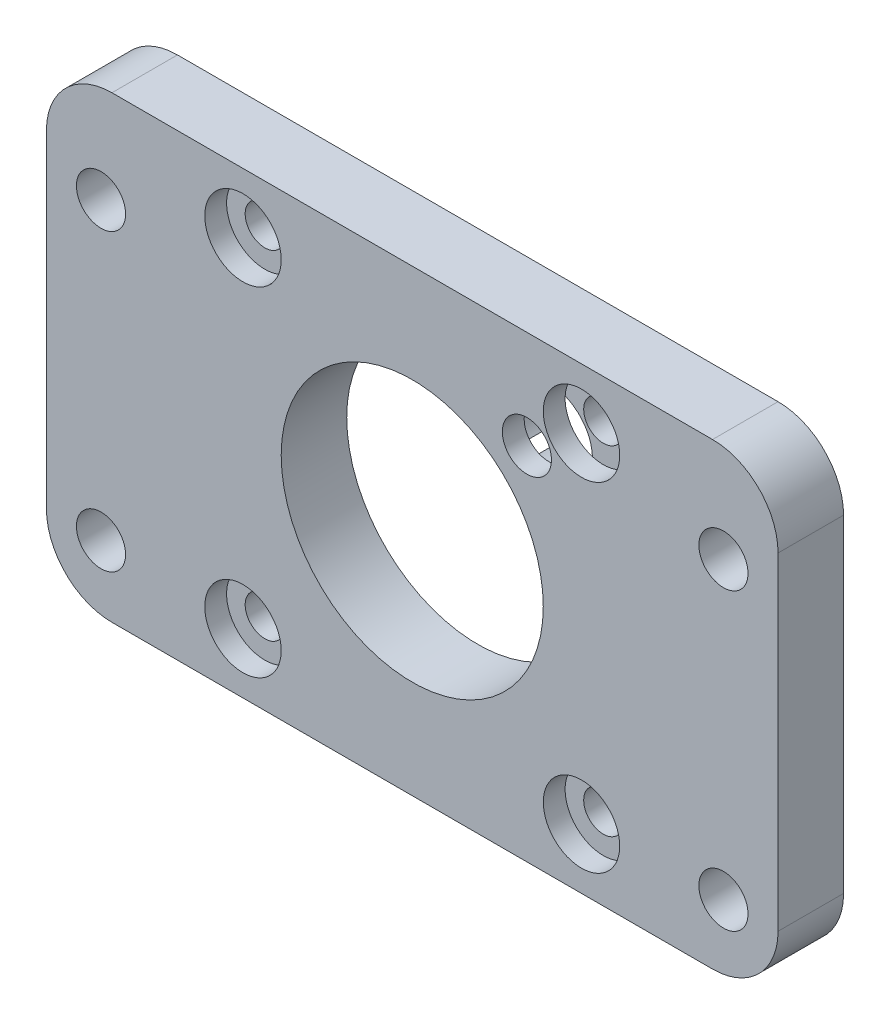
SolidWorks part; units mm, degrees
ref_plane "Спереди" through (0, 0, 0) normal (0, 0, 1) x (1, 0, 0)
ref_plane "Сверху" through (0, 0, 0) normal (0, 1, 0) x (1, 0, 0)
ref_plane "Справа" through (0, 0, 0) normal (1, 0, 0) x (0, 0, -1)
sketch "Эскиз1" plane through (0, 0, 0) normal (0, 0, 1) x (1, 0, 0)
  line L1 (0, 0) -> (67, 0)
  line L2 (0, 0) -> (0, 42)
  line L3 (0, 42) -> (67, 42)
  line L4 (67, 0) -> (67, 42)
  dimension "D1" = 42
  dimension "D2" = 67
extrude "Бобышка-Вытянуть1" add sketch "Эскиз1" along normal blind 6
sketch "Эскиз2" plane through (0, 0, 0) normal (0, 0, -1) x (-1, 0, 0)
  line L0 (-67, 42) -> (0, 42) construction
  line L1 (0, 0) -> (-67, 0) construction
  line L2 (0, 42) -> (0, 0) construction
  line L3 (-67, 0) -> (-67, 42) construction
  circle A0 centre (-62, 6) radius 2.25
  circle A1 centre (-62, 33) radius 2.25
  circle A2 centre (-5, 6) radius 2.25
  circle A3 centre (-5, 33) radius 2.25
  dimension "D1" = 4.5
  dimension "D2" = 9
  dimension "D3" = 6
  dimension "D4" = 5
  dimension "D5" = 5
extrude "Вырез-Вытянуть1" cut sketch "Эскиз2" against normal blind 9
fillet "Скругление1" radius 6 4 edges at (0, 0, 3) (0, 42, 3) (67, 0, 3) (67, 42, 3)
sketch "Эскиз3" plane through (0, 0, 0) normal (0, 0, -1) x (-1, 0, 0)
  line L0 (-49, 36.5) -> (-49, 5.5) construction
  line L1 (-49, 5.5) -> (-18, 5.5) construction
  line L2 (-67, 6) -> (-67, 36) construction
  line L3 (-61, 42) -> (-6, 42) construction
  circle A0 centre (-33.5, 21) radius 12
  circle A1 centre (-18, 36.5) radius 1.8
  circle A2 centre (-18, 5.5) radius 1.8
  circle A3 centre (-49, 5.5) radius 1.8
  circle A4 centre (-49, 36.5) radius 1.8
  point P11 (-33.5, 5.5)
  point P13 (-49, 21)
  point P16 (-67, 21)
  point P19 (-33.5, 42)
  dimension "D3" = 3.6
  dimension "D4" = 24
  dimension "D1" = 31
  dimension "D2" = 31
extrude "Вырез-Вытянуть2" cut sketch "Эскиз3" against normal blind 10
sketch "Эскиз4" plane through (0, 0, 6) normal (0, 0, 1) x (1, 0, 0)
  circle A0 centre (18, 5.5) radius 3.5
  circle A1 centre (18, 36.5) radius 3.5
  circle A2 centre (49, 5.5) radius 3.5
  circle A3 centre (49, 36.5) radius 3.5
  circle A4 centre (18, 5.5) radius 1.8 construction
  dimension "D1" = 7
extrude "Вырез-Вытянуть3" cut sketch "Эскиз4" against normal blind 2
sketch "Эскиз8" plane through (0, 0, 0) normal (0, 0, -1) x (-1, 0, 0)
  line L0 (-5, 33) -> (-62, 33) construction
  line L1 (-67, 6) -> (-67, 36) construction
  circle A0 centre (-44, 33) radius 2.25
  circle A2 centre (-44, 33) radius 4
  dimension "D1" = 4.5
  dimension "D2" = 8
  dimension "D3" = 23
extrude "Вырез-Вытянуть6" cut sketch "Эскиз8" against normal blind 4
extrude "Вырез-Вытянуть7" cut sketch "Эскиз8<2>" against normal blind 26 contours L0 A0 | A0 L0 region at (44, 32.0451, 0) region at (44, 33.9549, 0)
sketch "Эскиз8<2>" plane through (0, 0, 0) normal (0, 0, -1) x (-1, 0, 0) same geometry as "Эскиз8"
